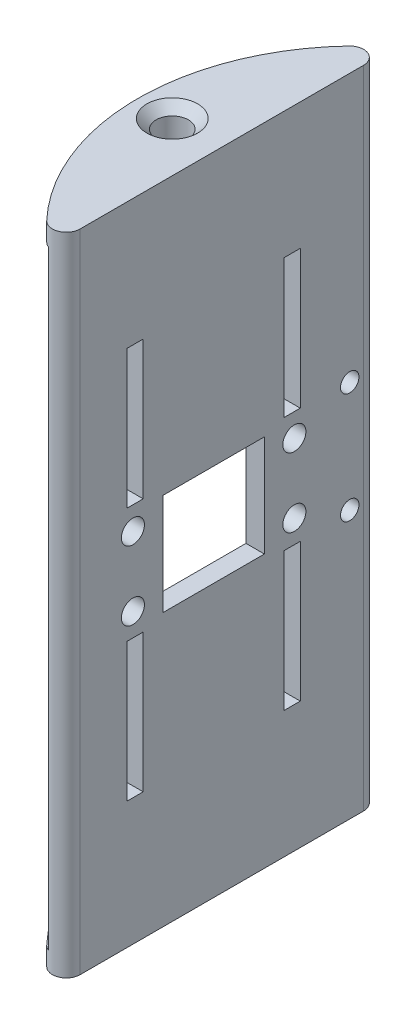
SolidWorks part; units mm, degrees
ref_plane "Front Plane" through (0, 0, 0) normal (1, 0, 0) x (0, 1, 0)
ref_plane "Top Plane" through (0, 0, 0) normal (0, 0, 1) x (0, 1, 0)
ref_plane "Right Plane" through (0, 0, 0) normal (0, 1, 0) x (-1, 0, 0)
sketch "Sketch1" plane through (0, 0, 0) normal (0, 0, 1) x (0, 1, 0)
  line L0 (-8.186, 0) -> (-8.186, -21.2483)
  line L1 (-8.186, -21.2483) -> (131.814, -21.2483)
  line L2 (131.814, -21.2483) -> (131.814, 0)
  line L3 (131.814, 0) -> (123.814, 0)
  line L4 (123.814, 0) -> (123.814, -17.2483)
  line L5 (123.814, -17.2483) -> (-0.186, -17.2483)
  line L6 (-0.186, -17.2483) -> (-0.186, 0)
  line L7 (-0.186, 0) -> (-8.186, 0)
  line L8 (-12.186, -30.6238) -> (-12.186, -16.002) construction
  line L10 (135.814, -16.002) -> (135.814, 53.9758) construction
  dimension "D1" = 4
  dimension "D2" = 8
  dimension "D3" = 4
  dimension "D4" = 4
  dimension "D5" = 140
extrude "Boss-Extrude1" add sketch "Sketch1" along normal blind 75
sketch "Sketch2" plane through (0, -8.186, 0) normal (0, -1, 0) x (1, 0, 0)
  line L0 (21.2483, 37.5) -> (0, 37.5) construction
  line L1 (21.2483, 75) -> (21.2483, 0) construction
  line L2 (0, 75) -> (0, 0) construction
  circle A0 centre (10.5, 37.5) radius 3.5
  dimension "D1" = 7
  dimension "D2" = 7
extrude "Cut-Extrude1" cut sketch "Sketch2" against normal offset from surface (7 mm away) 1 up to face at (8.6242, -0.186, 37.5)
sketch "Sketch3" plane through (0, 131.814, 0) normal (0, 1, 0) x (-1, 0, 0)
  circle A0 centre (-10.5, 37.5) radius 3.5 construction
  circle A1 centre (-10.5, 37.5) radius 3.5
extrude "Cut-Extrude2" cut sketch "Sketch3" against normal offset from surface (7 mm away) 1 up to face at (8.6242, 123.814, 37.5)
sketch "Sketch6" plane through (0, -0.186, 0) normal (0, 1, 0) x (-1, 0, 0)
  line L4 (-17.2483, 0) -> (0, 0)
  line L5 (0, 0) -> (0, 75)
  line L6 (0, 75) -> (-17.2483, 75)
  line L7 (-17.2483, 75) -> (-17.2483, 0)
  line L8 (-17.2483, 0) -> (0, 0)
  line L9 (0, 0) -> (0, 75)
  line L10 (0, 75) -> (-17.2483, 75)
  line L11 (-17.2483, 75) -> (-17.2483, 0)
  circle A1 centre (-10.5, 37.5) radius 4
  circle A3 centre (-10.5, 37.5) radius 3.5 construction
  dimension "D2" = 8
  dimension "D1" = 0
extrude "Cut-Extrude3" cut sketch "Sketch6" against normal blind 4
sketch "Sketch7" plane through (0, 123.814, 0) normal (0, -1, 0) x (1, 0, 0)
  line L4 (0, 0) -> (17.2483, 0)
  line L5 (17.2483, 0) -> (17.2483, 75)
  line L6 (17.2483, 75) -> (0, 75)
  line L7 (0, 75) -> (0, 0)
  line L8 (0, 0) -> (17.2483, 0)
  line L9 (17.2483, 0) -> (17.2483, 75)
  line L10 (17.2483, 75) -> (0, 75)
  line L11 (0, 75) -> (0, 0)
  circle A2 centre (10.5, 37.5) radius 4
  circle A3 centre (10.5, 37.5) radius 3.5 construction
  dimension "D1" = 8
  dimension "D2" = 0
extrude "Cut-Extrude4" cut sketch "Sketch7" against normal blind 4
fillet "Fillet6" radius 4 2 edges at (10.5, 127.814, 33.5) (10.5, -4.186, 41.5)
chamfer "Chamfer1" distance 2 angle 45 2 edges at (10.5, -8.186, 34) (10.5, 131.814, 41)
sketch "Sketch10" plane through (0, -8.186, 0) normal (0, -1, 0) x (1, 0, 0)
  line L6 (21.2483, 75) -> (0, 75)
  line L7 (0, 75) -> (0, 0) construction
  line L8 (0, 75) -> (21.2483, 75) construction
  line L9 (0, 75) -> (0, 0)
  line L10 (0, 0) -> (21.2483, 0)
  arc A1 (21.2483, 75) -> (21.2483, 0) centre (50.6551, 37.5) ccw
  circle A4 centre (10.5, 37.5) radius 5.5 construction
  dimension "D1" = 2
extrude "Cut-Extrude9" cut sketch "Sketch10" against normal through all
fillet "Fillet11" radius 3 2 edges at (21.2483, 61.814, 75) (21.2483, 61.814, 0)
sketch "Sketch14" plane through (21.2483, 0, 0) normal (1, 0, 0) x (0, 1, 0)
  line L2 (131.814, 5.8571) -> (131.814, 74.4281) construction
  line L3 (-8.186, 74.4281) -> (-8.186, 5.8571) construction
  line L4 (-8.186, 40.1426) -> (131.814, 40.1426) construction
  line L5 (61.814, 8.6855) -> (61.814, 71.5997) construction
  line L8 (104.314, 58.0522) -> (74.314, 58.0522)
  line L9 (19.314, 54.5522) -> (49.314, 54.5522)
  line L10 (19.314, 54.5522) -> (19.314, 58.0522)
  line L11 (19.314, 58.0522) -> (49.314, 58.0522)
  line L12 (49.314, 54.5522) -> (49.314, 58.0522)
  line L13 (19.314, 54.5522) -> (49.314, 58.0522) construction
  line L14 (19.314, 58.0522) -> (49.314, 54.5522) construction
  line L15 (74.314, 54.5522) -> (74.314, 58.0522)
  line L16 (104.314, 54.5522) -> (74.314, 54.5522)
  line L17 (104.314, 54.5522) -> (104.314, 58.0522)
  line L18 (54.314, 56.7774) -> (54.314, 21.7774) construction
  line L19 (54.314, 39.2774) -> (68.2197, 39.2774) construction
  line L20 (104.314, 24.0026) -> (104.314, 20.5026)
  line L21 (104.314, 24.0026) -> (74.314, 24.0026)
  line L22 (74.314, 24.0026) -> (74.314, 20.5026)
  line L23 (104.314, 20.5026) -> (74.314, 20.5026)
  line L24 (19.314, 20.5026) -> (49.314, 20.5026)
  line L25 (49.314, 24.0026) -> (49.314, 20.5026)
  line L26 (19.314, 24.0026) -> (49.314, 24.0026)
  line L27 (19.314, 24.0026) -> (19.314, 20.5026)
  line L28 (-8.186, 68.2226) -> (-8.186, 6.7774) construction
  line L29 (131.814, 68.2226) -> (131.814, 6.7774) construction
  line L30 (-8.186, 6.7774) -> (131.814, 6.7774) construction
  circle A0 centre (54.314, 21.7774) radius 2.5
  circle A1 centre (54.314, 56.7774) radius 2.5
  circle A2 centre (69.314, 56.7774) radius 2.5
  circle A3 centre (69.314, 21.7774) radius 2.5
  circle A4 centre (49.814, 9.7774) radius 2
  circle A5 centre (73.814, 9.7774) radius 2
  point P24 (34.314, 56.3022)
  point P45 (61.814, 6.7774)
  dimension "D3" = 2.5
  dimension "D4" = 5
  dimension "D8" = 4
  dimension "D1" = 3.5
  dimension "D2" = 30
  dimension "D5" = 15
  dimension "D6" = 35
  dimension "D7" = 15
  dimension "D9" = 24
  dimension "D10" = 3
extrude "Cut-Extrude13" cut sketch "Sketch14" against normal up to next
sketch "Sketch16" plane through (21.2483, 0, 0) normal (1, 0, 0) x (0, 1, 0)
  line L0 (54.314, 21.7774) -> (69.314, 56.7774) construction
  line L1 (54.314, 56.7774) -> (69.314, 21.7774) construction
  line L3 (50.814, 28.2774) -> (72.814, 28.2774)
  line L4 (50.814, 28.2774) -> (50.814, 50.2774)
  line L5 (50.814, 50.2774) -> (72.814, 50.2774)
  line L6 (72.814, 28.2774) -> (72.814, 50.2774)
  line L7 (50.814, 28.2774) -> (72.814, 50.2774) construction
  line L8 (50.814, 50.2774) -> (72.814, 28.2774) construction
  point P8 (61.814, 39.2774)
  dimension "D1" = 22
extrude "Cut-Extrude14" cut sketch "Sketch16" against normal up to next
sketch "Sketch17" plane through (17.2483, 0, 0) normal (-1, 0, 0) x (0, -1, 0)
  line L0 (-127.814, 43.0156) -> (-3.6818, 43.0156) construction
  line L7 (-41.814, 50) -> (-39.814, 50)
  line L8 (-41.814, 50) -> (-41.814, 42.5)
  line L9 (-41.814, 42.5) -> (-39.814, 42.5)
  line L10 (-39.814, 50) -> (-39.814, 42.5)
  line L11 (-28.814, 50) -> (-26.814, 50)
  line L12 (-28.814, 50) -> (-28.814, 42.5)
  line L13 (-28.814, 42.5) -> (-26.814, 42.5)
  line L14 (-26.814, 50) -> (-26.814, 42.5)
  line L15 (-49.314, 58.0522) -> (-49.314, 54.5522) construction
  line L16 (-26.814, 25) -> (-26.814, 43.5312)
  line L17 (-28.814, 43.5312) -> (-26.814, 43.5312)
  line L18 (-28.814, 25) -> (-28.814, 43.5312)
  line L19 (-28.814, 25) -> (-26.814, 25)
  line L20 (-39.814, 13.9688) -> (-39.814, 43.5312)
  line L21 (-41.814, 43.5312) -> (-39.814, 43.5312)
  line L22 (-41.814, 13.9688) -> (-41.814, 43.5312)
  line L23 (-41.814, 13.9688) -> (-39.814, 13.9688)
  line L24 (-127.814, 40.5312) -> (-127.814, 45.5) construction
  line L25 (-41.814, 46.25) -> (-39.814, 46.25) construction
  line L26 (-39.814, 28.75) -> (-41.814, 28.75) construction
  dimension "D1" = 11
  dimension "D2" = 2
  dimension "D3" = 7.5
  dimension "D4" = 17.5
  dimension "D5" = 7.5
sketch "Sketch18" plane through (0, -0.186, 0) normal (0, 1, 0) x (-1, 0, 0)
  circle A0 centre (-10.5, 37.5) radius 2
  dimension "D1" = 4
extrude "Cut-Extrude15" cut sketch "Sketch18" against normal through all both and the other way through all
ref_plane "Plane1" through (0, 41.814, 0) normal (0, -1, 0) x (1, 0, 0)
